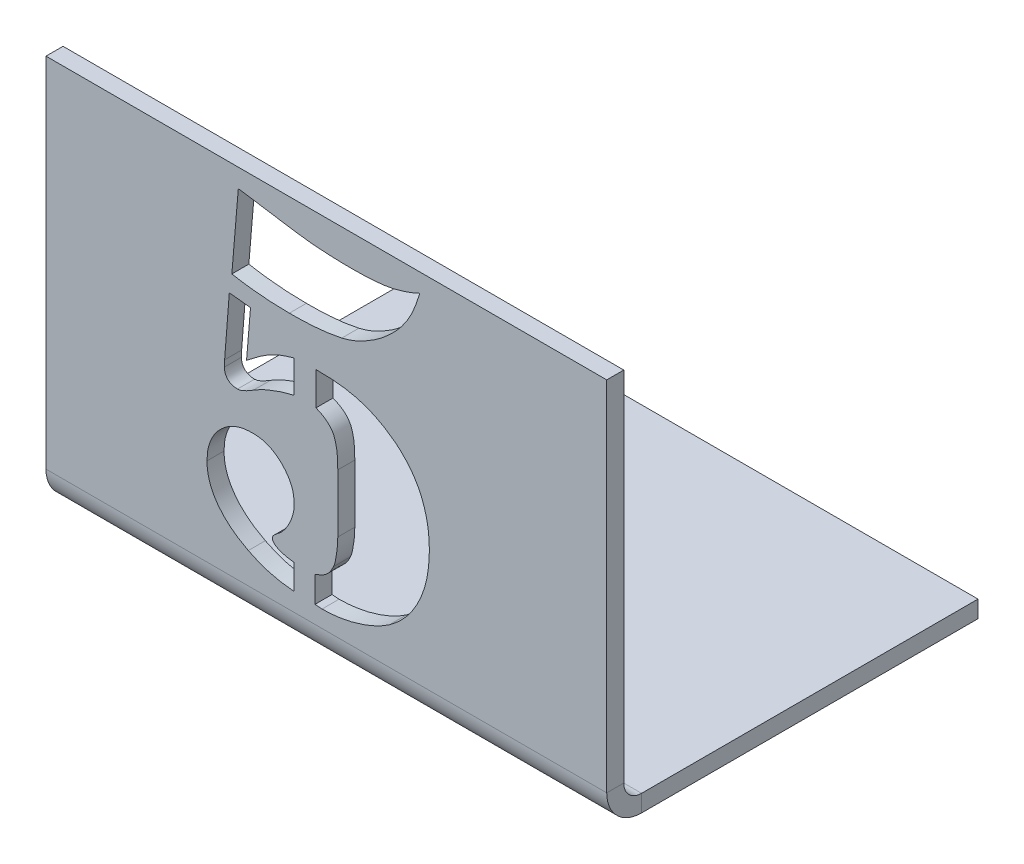
SolidWorks part; units mm, degrees
note: The reader was unsure of these and kept them because the rebuilt part matched: flange length of "Edge-Flange1".
material "16 Ga. SHEET METAL"
ref_plane "Front Plane" through (0, 0, 0) normal (0, 0, 1) x (1, 0, 0)
ref_plane "Top Plane" through (0, 0, 0) normal (0, 1, 0) x (1, 0, 0)
ref_plane "Right Plane" through (0, 0, 0) normal (1, 0, 0) x (0, 0, -1)
sketch "Sketch1" plane through (0, 0, 0) normal (0, 1, 0) x (1, 0, 0)
  line L1 (-25, 0) -> (25, 0)
  line L2 (-25, 0) -> (-25, 30)
  line L3 (-25, 30) -> (25, 30)
  line L4 (25, 0) -> (25, 30)
  dimension "D1" = 30
  dimension "D2" = 50
base flange "Base-Flange1" sketch "Sketch1" thickness 1.5189 reverse thickness direction yes parameters "D1"=1.5875
edge flange "Edge-Flange1" sketch "Sketch8" flange angle 90 flange length 35 flange position bend outside bend radius 1.5875 thickness 1.5189 relief rectangular parameters "D6"=10
sketch "Sketch8" plane through (0, 1.5189, 0) normal (0, 0, 1) x (1, 0, 0)
  line L0 (-25, 0) -> (25, 0) construction
  line L1 (-25, 0) -> (25, 0)
  line L2 (-25, 0) -> (-25, 33.4811)
  line L3 (-25, 33.4811) -> (25, 33.4811)
  line L4 (25, 33.4811) -> (25, 0)
bend "EdgeBend1" bend radius 1.5875 bend angle 90 parameters "D5"=1
hole_wizard "M8 Clearance Hole1" positions "Sketch9" profile "Sketch10" hole size "M8" standard "Peddi DIN" end condition through all
sketch "Sketch9" plane through (0, 1.5189, 0) normal (0, 1, 0) x (1, 0, 0)
  line L0 (25, -3.1064) -> (-25, -3.1064) construction
  line L1 (-25, 30) -> (-25, 0) construction
  point P0 (-13, 21.8936)
  dimension "D1" = 25
  dimension "D2" = 12
sketch "Sketch10" plane through (-13, 1.5189, -21.8936) normal (1, 0, 0) x (0, 0, 1)
  line L0 (0, 0) -> (0, 1.5189)
  line L1 (0, 1.5189) -> (4.5, 1.5189)
  line L2 (4.5, 1.5189) -> (4.5, 0)
  line L5 (4.5, 0) -> (0, 0)
  line L11 (0, -6.35) -> (0, 107.95) construction
  dimension "Thru Hole Dia." = 9
  dimension "Thru Hole Depth" = 1.5189
sketch "Sketch11" plane through (0, 0, 3.1064) normal (0, 0, 1) x (1, 0, 0)
  line L0 (-25, 0) -> (25, 0) construction
  text T0 "5" font "Stencil" height 28
  dimension "D1" = 5
extrude "Cut-Extrude1" cut sketch "Sketch11" against normal through all
other "Freeze***"
sketch "Bend-Lines1" [suppressed] plane through (0, 0, 0) normal (0, 1, 0) x (1, 0, 0)
sketch "Bounding-Box1" [suppressed] plane through (0, 0, 0) normal (0, 1, 0) x (1, 0, 0)
sheet metal parameters "Sheet-Metal1" thickness 1.5189 parameters "D1"=1.5875
flat pattern "Flat-Pattern1" [suppressed]
sketch "Bend-Lines2" plane through (0, 0, 0) normal (0, 1, 0) x (1, 0, 0)
sketch "Bounding-Box2" [suppressed] plane through (0, 0, 0) normal (0, 1, 0) x (1, 0, 0)
sheet metal parameters "Sheet-Metal2" thickness 1.5189 parameters "D1"=1.5875
flat pattern "Flat-Pattern1" [suppressed]
sketch "Bend-Lines2" plane through (0, 0, 0) normal (0, 1, 0) x (1, 0, 0)
sketch "Bounding-Box2" [suppressed] plane through (0, 0, 0) normal (0, 1, 0) x (1, 0, 0)
bend of the flat pattern "Flatten-<EdgeBend1>1"
sheet metal parameters "Sheet-Metal3" thickness 1.5189 parameters "D1"=1.5875
flat pattern "Flat-Pattern1" [suppressed]
sketch "Bend-Lines2" plane through (0, 0, 0) normal (0, 1, 0) x (1, 0, 0)
sketch "Bounding-Box2" [suppressed] plane through (0, 0, 0) normal (0, 1, 0) x (1, 0, 0)
bend of the flat pattern "Flatten-<EdgeBend1>1"
sheet metal parameters "Sheet-Metal4" thickness 1.5189 parameters "D1"=1.5875
flat pattern "Flat-Pattern1"
sketch "Bend-Lines2" plane through (0, 0, 0) normal (0, -1, 0) x (-1, 0, 0)
  line L0 (-25, -1.724) -> (25, -1.724) construction
  line L1 (-25, -1.724) -> (25, -1.724) construction
sketch3d "Bounding-Box2" [suppressed]
  line L0 (25, -35.3416, 0) -> (25, 30, 0) construction
  line L1 (-25, -35.3416, 0) -> (-25, 30, 0) construction
  line L2 (25, -35.3416, 0) -> (-25, -35.3416, 0) construction
  line L3 (25, 30, 0) -> (-25, 30, 0) construction
bend of the flat pattern "Flatten-<EdgeBend1>1"
